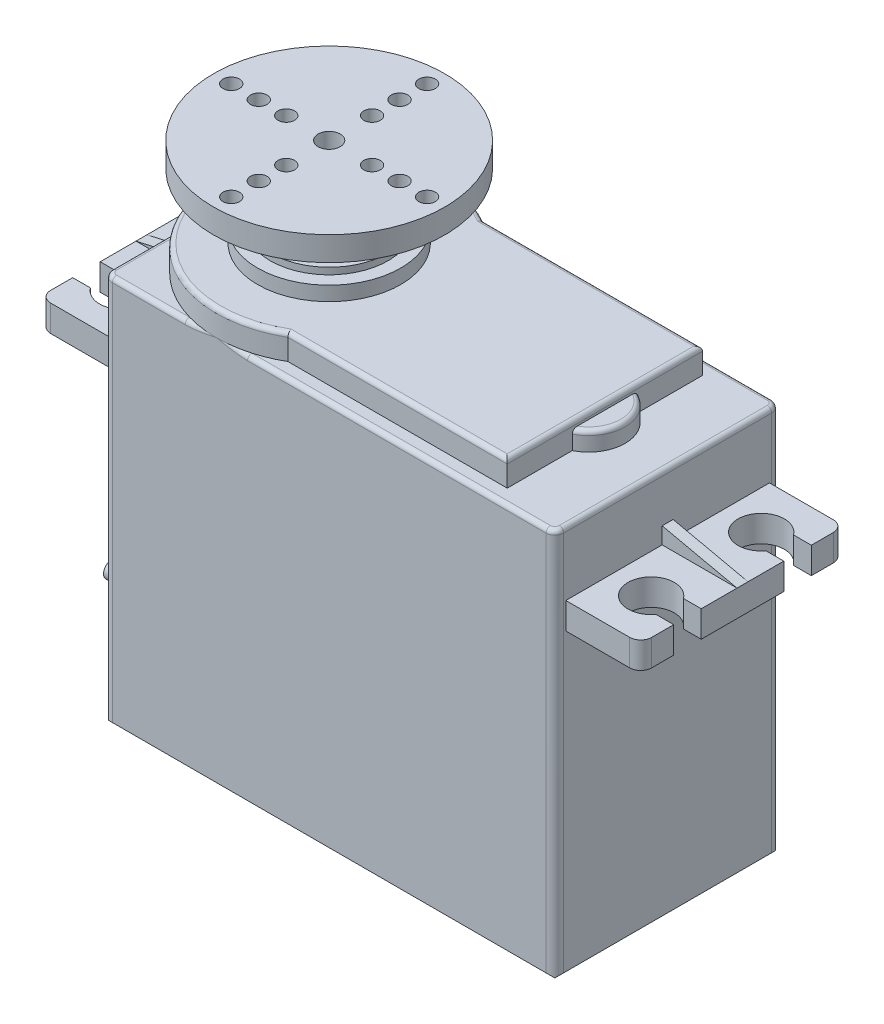
SolidWorks part; units mm, degrees
ref_plane "Front Plane" through (0, 0, 0) normal (0, 0, 1) x (1, 0, 0)
ref_plane "Top Plane" through (0, 0, 0) normal (0, 1, 0) x (1, 0, 0)
ref_plane "Right Plane" through (0, 0, 0) normal (1, 0, 0) x (0, 0, -1)
sketch "Sketch1" plane through (0, 0, 0) normal (0, 1, 0) x (1, 0, 0)
  line L1 (-20.5, -10.25) -> (20.5, -10.25)
  line L2 (-20.5, -10.25) -> (-20.5, 10.25)
  line L3 (-20.5, 10.25) -> (20.5, 10.25)
  line L4 (20.5, -10.25) -> (20.5, 10.25)
  line L5 (-20.5, -10.25) -> (20.5, 10.25) construction
  line L6 (-20.5, 10.25) -> (20.5, -10.25) construction
  point P0 (0, 0)
  dimension "D1" = 41
  dimension "D2" = 20.5
extrude "Boss-Extrude1" add sketch "Sketch1" along normal blind 37
sketch "Sketch2" plane through (0, 37, 0) normal (0, 1, 0) x (1, 0, 0)
  line L0 (-20.5, 10.25) -> (-20.5, -10.25) construction
  line L1 (20.5, -10.25) -> (20.5, 10.25) construction
  line L2 (-5.122, -8.875) -> (14.8, -8.875)
  line L4 (-5.122, 8.875) -> (14.8, 8.875)
  line L5 (14.8, -8.875) -> (14.8, -2.9672)
  line L9 (14.8, 2.9672) -> (14.8, 8.875)
  arc A0 (-5.122, 8.875) -> (-5.122, -8.875) centre (-10.25, 0) ccw
  arc A1 (14.8, -2.9672) -> (14.8, 2.9672) centre (13.3208, 0) ccw
  point P5 (4.4919, 0)
  dimension "D1" = 10.25
  dimension "D2" = 17.75
  dimension "D3" = 5.7
extrude "Boss-Extrude2" add sketch "Sketch2" along normal blind 2.3
sketch "Sketch3" plane through (0, 39.3, 0) normal (0, 1, 0) x (1, 0, 0)
  circle A0 centre (-10.25, 0) radius 6.5
  dimension "D1" = 13
extrude "Boss-Extrude3" add sketch "Sketch3" along normal blind 1.3
sketch "Sketch4" plane through (0, 40.6, 0) normal (0, 1, 0) x (1, 0, 0)
  circle A0 centre (-10.25, 0) radius 5.35
  dimension "D1" = 10.7
extrude "Boss-Extrude4" add sketch "Sketch4" along normal blind 0.6
sketch "Sketch5" plane through (0, 39.3, 0) normal (0, 1, 0) x (1, 0, 0)
  line L0 (14.8, 2.9672) -> (14.8, -2.9672)
  arc A0 (14.8, -2.9672) -> (14.8, 2.9672) centre (13.3208, 0) ccw construction
  arc A1 (14.8, -2.9672) -> (14.8, 2.9672) centre (13.3208, 0) ccw
extrude "Cut-Extrude1" cut sketch "Sketch5" against normal blind 0.6
sketch "Sketch6" plane through (0, 41.2, 0) normal (0, 1, 0) x (1, 0, 0)
  circle A0 centre (-10.25, 0) radius 3
  dimension "D1" = 6
extrude "Boss-Extrude5" add sketch "Sketch6" along normal blind 4
chamfer "Chamfer1" distance 2 angle 45 4 edges at (-20.5, 0, 0) (0, 0, -10.25) (20.5, 0, 0) (0, 0, 10.25)
fillet "Fillet2" radius 0.8 4 edges at (-20.5, 19.5, -10.25) (-20.5, 19.5, 10.25) (20.5, 19.5, -10.25) (20.5, 19.5, 10.25)
sketch "Sketch7" plane through (-20.5, 0, 0) normal (-1, 0, 0) x (0, 0, 1)
  line L1 (-9.25, 31.2) -> (9.25, 31.2)
  line L2 (-9.25, 31.2) -> (-9.25, 28.8)
  line L3 (-9.25, 28.8) -> (9.25, 28.8)
  line L4 (9.25, 31.2) -> (9.25, 28.8)
  line L6 (-9.45, 37) -> (0, 37) construction
  line L9 (-10.25, 37) -> (-10.25, 2) construction
  dimension "D1" = 5.8
  dimension "D2" = 2.4
  dimension "D3" = 18.5
  dimension "D4" = 1
extrude "Boss-Extrude6" add sketch "Sketch7" along normal blind 6.8
sketch "Sketch9" plane through (0, 31.2, 0) normal (0, 1, 0) x (1, 0, 0)
  line L0 (-27.3, -9.25) -> (-27.3, 9.25) construction
  line L3 (-25.6875, 6.25) -> (-27.3, 6.25)
  line L4 (-21.6, 3.75) -> (-22.3125, 3.75)
  line L5 (-21.6, 3.75) -> (-21.6, 6.25)
  line L6 (-21.6, 6.25) -> (-22.3125, 6.25)
  line L7 (-27.3, 3.75) -> (-27.3, 6.25)
  line L8 (-21.6, 3.75) -> (-24, 5) construction
  line L9 (-21.6, 6.25) -> (-24, 5) construction
  line L10 (-21.6, -6.25) -> (-27.3, -6.25)
  line L11 (-21.6, -6.25) -> (-21.6, -3.75)
  line L12 (-21.6, -3.75) -> (-27.3, -3.75)
  line L13 (-27.3, -6.25) -> (-27.3, -3.75)
  line L14 (-21.6, -6.25) -> (-24, -5) construction
  line L15 (-21.6, -3.75) -> (-24, -5) construction
  line L18 (-25.6875, 3.75) -> (-27.3, 3.75)
  arc A0 (-25.6875, 3.75) -> (-25.6875, 6.25) centre (-24, 5) ccw
  arc A1 (-25.6875, -6.25) -> (-25.6875, -3.75) centre (-24, -5) ccw
  line M4 (-27.3, 9.25) -> (-27.3, -9.25)
  dimension "D1" = 4.2
  dimension "D2" = 4.2
  dimension "D3" = 3.3
  dimension "D4" = 10
  dimension "D5" = 5
  dimension "D6" = 2.5
  dimension "D7" = 2.5
  dimension "D8" = 3.3
extrude "Cut-Extrude2" cut sketch "Sketch9" against normal blind 6.8 contours A0 L3 L18 M4 | L12 A1 | L10 A1 | L10 A1 L12 M4 region at (-24.5093, 31.2, -5) region at (-24.6644, 31.2, 5) region at (-24, 31.2, 3.4033) region at (-24, 31.2, 6.5967)
fillet "Fillet1" radius 1 2 edges at (-27.3, 30, 9.25) (-27.3, 30, -9.25)
sketch "Sketch10" plane through (0, 31.2, 0) normal (0, 1, 0) x (1, 0, 0)
  line L0 (-20.5, -9.25) -> (-20.5, 9.25) construction
  line L1 (-27.3, -0.5) -> (-20.5, -0.5)
  line L2 (-27.3, -0.5) -> (-27.3, 0.5)
  line L3 (-27.3, 0.5) -> (-20.5, 0.5)
  line L4 (-20.5, -0.5) -> (-20.5, 0.5)
  line L5 (-27.3, -0.5) -> (-20.5, 0.5) construction
  line L6 (-27.3, 0.5) -> (-20.5, -0.5) construction
  line L7 (-27.3, -3.75) -> (-27.3, 3.75) construction
  point P0 (-23.9, 0)
  dimension "D1" = 1
extrude "Boss-Extrude7" add sketch "Sketch10" along normal blind 1.5
sketch "Sketch11" plane through (0, 0, 0.5) normal (0, 0, 1) x (1, 0, 0)
  line L0 (-27.3, 31.2) -> (-20.5, 32.7)
  line L1 (-20.5, 32.7) -> (-27.3, 32.7)
  line L2 (-27.3, 32.7) -> (-27.3, 31.2)
extrude "Cut-Extrude3" cut sketch "Sketch11" against normal blind 1.5
ref_plane "Plane1" through (0, 0, 0) normal (-1, 0, 0) x (0, 0, 1)
mirror "Mirror2" about plane through (0, 0, 0) normal (-1, 0, 0) of "Fillet1", "Cut-Extrude2", "Boss-Extrude6", "Cut-Extrude3", "Boss-Extrude7"
sketch "Sketch12" plane through (0, 45.2, 0) normal (0, 1, 0) x (1, 0, 0)
  circle A0 centre (-10.25, 0) radius 1.25
  dimension "D1" = 2.5
extrude "Cut-Extrude4" cut sketch "Sketch12" against normal blind 4
fillet "Fillet5" radius 0.4 5 edges at (16.6363, 38.7, 0) (14.8, 39.3, 0) (4.839, 39.3, -8.875) (-20.5, 39.3, 0) (4.839, 39.3, 8.875)
fillet "Fillet7" radius 0.4 11 edges at (20.2657, 37, 10.0157) (4.725, 37, 10.25) (-14.975, 37, 10.25) (-20.2657, 37, 10.0157) (-20.5, 37, 4.725) (-20.5, 37, -4.725) (-20.2657, 37, -10.0157) (-14.975, 37, -10.25) (4.725, 37, -10.25) (20.2657, 37, -10.0157) (20.5, 37, 0)
sketch "Sketch13" plane through (-20.5, 0, 0) normal (-1, 0, 0) x (0, 0, 1)
  line L0 (8.25, 0) -> (-8.25, 0) construction
  line L1 (-3.5, 3.2) -> (3.5, 3.2)
  line L2 (-3.5, 3.2) -> (-3.5, 7.4)
  line L3 (-3.5, 7.4) -> (3.5, 7.4)
  line L4 (3.5, 3.2) -> (3.5, 7.4)
  line L5 (-3.5, 3.2) -> (3.5, 7.4) construction
  line L6 (-3.5, 7.4) -> (3.5, 3.2) construction
  point P0 (0, 5.3)
  dimension "D1" = 7
  dimension "D2" = 4.2
  dimension "D3" = 3.2
extrude "Boss-Extrude8" add sketch "Sketch13" along normal blind 1
sketch "Sketch14" plane through (-21.5, 0, 0) normal (-1, 0, 0) x (0, 0, 1)
  line L9 (3.15, 3.55) -> (3.15, 7.05)
  line L10 (3.15, 7.05) -> (-3.15, 7.05)
  line L11 (-3.15, 7.05) -> (-3.15, 3.55)
  line L12 (-3.15, 3.55) -> (3.15, 3.55)
  line L13 (3.15, 3.55) -> (3.15, 7.05)
  line L14 (3.15, 7.05) -> (-3.15, 7.05)
  line L15 (-3.15, 7.05) -> (-3.15, 3.55)
  line L16 (-3.15, 3.55) -> (3.15, 3.55)
  dimension "D1" = 0.35
extrude "Boss-Extrude9" add sketch "Sketch14" along normal blind 4 draft 5 contours L14 L15 L16 L13
sketch "Sketch15" plane through (-25.5, 0, 0) normal (-1, 0, 0) x (0, 0, 1)
  line L0 (-2.8, 3.9) -> (2.8, 3.9) construction
  circle A0 centre (-1.5, 5.3) radius 0.75
  circle A1 centre (0, 5.3) radius 0.75
  circle A2 centre (1.5, 5.3) radius 0.75
  dimension "D1" = 1.5
  dimension "D2" = 1.5
  dimension "D3" = 1.5
  dimension "D4" = 1.4
extrude "Boss-Extrude12" add sketch "Sketch15" along normal blind 3 separate body contours A0 | A1 | A2 region at (-25.5, 5.3, -1.5) region at (-25.5, 5.3, 1.5) region at (-25.5, 5.3, 0)
sketch "Sketch16" plane through (0, 45.2, 0) normal (0, 1, 0) x (1, 0, 0)
  circle A0 centre (-10.25, 0) radius 10.5
  dimension "D1" = 21
extrude "Boss-Extrude13" add sketch "Sketch16" along normal blind 2.2
sketch "Sketch17" plane through (0, 47.4, 0) normal (0, 1, 0) x (1, 0, 0)
  circle A0 centre (-19.1465, 0) radius 0.75
  circle A1 centre (-16.6465, 0) radius 0.75
  circle A2 centre (-14.1465, 0) radius 0.75
  circle A3 centre (-10.25, 3.8965) radius 0.75
  circle A4 centre (-10.25, 6.3965) radius 0.75
  circle A5 centre (-10.25, 8.8965) radius 0.75
  circle A6 centre (-6.3535, 0) radius 0.75
  circle A7 centre (-3.8535, 0) radius 0.75
  circle A8 centre (-1.3535, 0) radius 0.75
  circle A9 centre (-10.25, -3.8965) radius 0.75
  circle A10 centre (-10.25, -6.3965) radius 0.75
  circle A11 centre (-10.25, -8.8965) radius 0.75
  point P3 (-10.25, 0)
  point P29 (-10.25, 0)
  dimension "D1" = 3
  dimension "D2" = 1.5
  dimension "D3" = 4
extrude "Cut-Extrude5" cut sketch "Sketch17" against normal up to next (2.2 mm away)
sketch "Sketch18" plane through (0, 47.4, 0) normal (0, 1, 0) x (1, 0, 0)
  circle A0 centre (-10.25, 0) radius 1.0032
extrude "Cut-Extrude6" cut sketch "Sketch18" against normal blind 3
